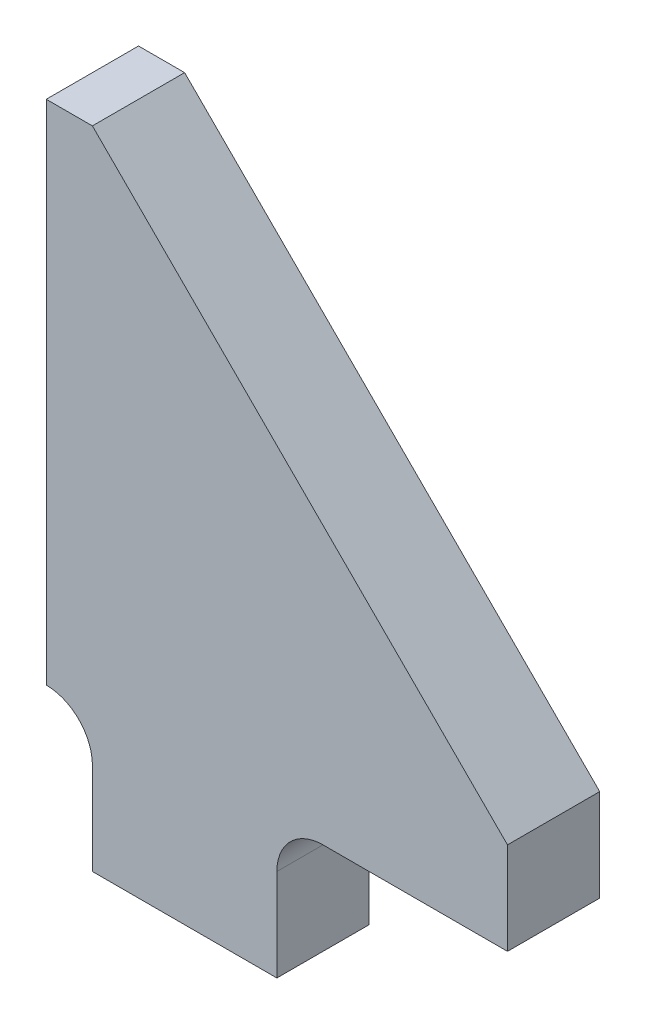
SolidWorks part; units mm, degrees
material "Plywood"
ref_plane "Plan de face" through (0, 0, 0) normal (0, 0, 1) x (1, 0, 0)
ref_plane "Plan de dessus" through (0, 0, 0) normal (0, 1, 0) x (1, 0, 0)
ref_plane "Plan de droite" through (0, 0, 0) normal (1, 0, 0) x (0, 0, -1)
sketch "Esquisse1" plane through (0, 0, 0) normal (0, 0, 1) x (1, 0, 0)
  line L0 (0, 0) -> (0, 11)
  line L1 (0, 11) -> (1, 11)
  line L2 (1, 11) -> (10, 2)
  line L3 (10, 2) -> (10, 0)
  line L4 (10, 0) -> (5, 0)
  line L5 (5, 0) -> (5, -3)
  line L6 (5, -3) -> (1, -3)
  line L7 (1, -3) -> (1, 0)
  line L8 (1, 0) -> (0, 0)
  dimension "D1" = 11
  dimension "D2" = 1
  dimension "D3" = 5
  dimension "D4" = 3
  dimension "D5" = 45
  dimension "D6" = 10
  dimension "D7" = 1
extrude "Boss.-Extru.1" add sketch "Esquisse1" along normal blind 2
fillet "Congé1" radius 1 2 edges at (1, 0, 1) (5, 0, 1)
